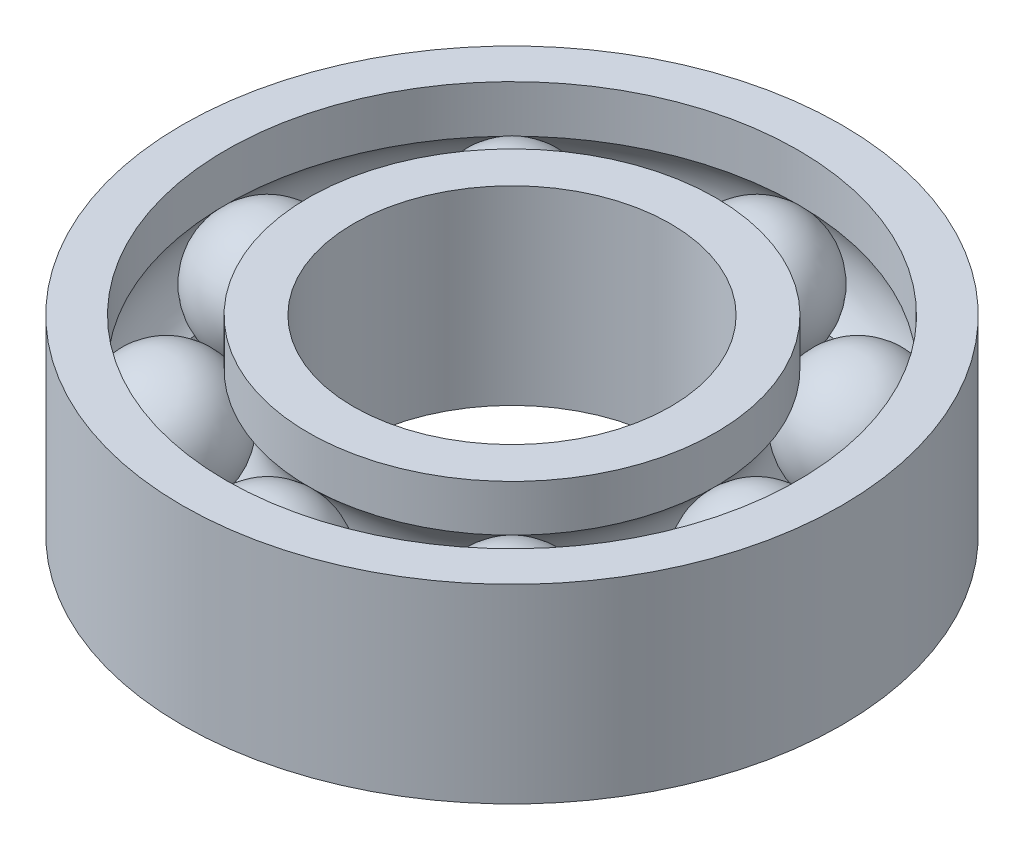
SolidWorks part; units mm, degrees
ref_plane "Front Plane" through (0, 0, 0) normal (0, 0, 1) x (1, 0, 0)
ref_plane "Top Plane" through (0, 0, 0) normal (0, 1, 0) x (1, 0, 0)
ref_plane "Right Plane" through (0, 0, 0) normal (1, 0, 0) x (0, 0, -1)
sketch "Sketch1" plane through (0, 0, 0) normal (0, 0, 1) x (1, 0, 0)
  line L0 (-22.5589, -3.7743) -> (-22.5589, -7.5)
  line L1 (-16.0589, 7.5) -> (-12.5, 7.5)
  line L2 (-16.0589, 7.5) -> (-16.0589, 3.8247)
  line L3 (-16.0589, -7.5) -> (-12.5, -7.5)
  line L4 (-12.5, 7.5) -> (-12.5, -7.5)
  line L5 (-16.0589, 7.5) -> (-12.5, -7.5) construction
  line L6 (-16.0589, -7.5) -> (-12.5, 7.5) construction
  line L7 (-26, 7.5) -> (-22.5589, 7.5)
  line L8 (-26, 7.5) -> (-26, -7.5)
  line L9 (-26, -7.5) -> (-22.5589, -7.5)
  line L10 (-22.5589, 7.5) -> (-22.5589, 3.7743)
  line L11 (-26, 7.5) -> (-22.5589, -7.5) construction
  line L12 (-26, -7.5) -> (-22.5589, 7.5) construction
  line L13 (-16.0589, -3.8247) -> (-16.0589, -7.5)
  line L14 (0, -15.9068) -> (0, 25.7223) construction
  line L15 (-19.2794, -5) -> (-19.2794, 5)
  line L16 (-19.2794, -6.1128) -> (-19.2794, 8.6995) construction
  arc A0 (-22.5589, 3.7743) -> (-22.5589, -3.7743) centre (-19.2794, 0) ccw
  arc A1 (-16.0589, -3.8247) -> (-16.0589, 3.8247) centre (-19.2794, 0) ccw
  arc A2 (-19.2794, 5) -> (-19.2794, -5) centre (-19.2794, 0) ccw
  point P0 (-14.2794, 0)
  point P5 (-24.2794, 0)
  dimension "D1" = 26
  dimension "D5" = 10
  dimension "D2" = 12.5
  dimension "D3" = 15
  dimension "D4" = 15
revolve "Revolve2" add sketch "Sketch1" angle 360 about L16 region at (-21.4015, 0, 0)
revolve "Revolve3" add sketch "Sketch1<5>" angle 360 about L14 region at (-24.4953, 0, 0) region at (-14.0522, 0, 0)
sketch "Sketch1<5>" plane through (0, 0, 0) normal (0, 0, 1) x (1, 0, 0) same geometry as "Sketch1"
pattern_circular "CirPattern1" count 8 over 360 of bodies 103
